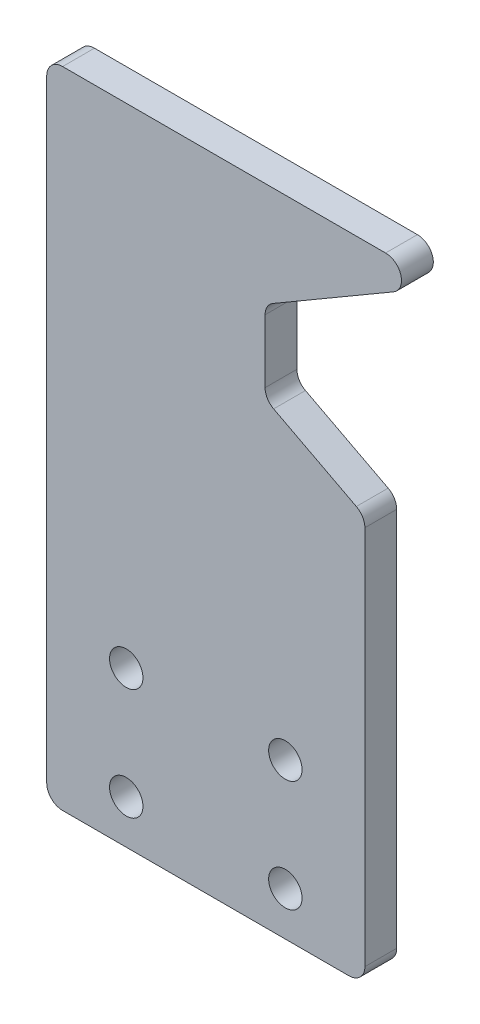
SolidWorks part; units mm, degrees
material "Thornel Mat VMA"
ref_plane "前视基准面" through (0, 0, 0) normal (0, 0, 1) x (1, 0, 0)
ref_plane "上视基准面" through (0, 0, 0) normal (0, 1, 0) x (1, 0, 0)
ref_plane "右视基准面" through (0, 0, 0) normal (1, 0, 0) x (0, 0, -1)
other "Configuration Table"
sketch "草图1" plane through (0, 0, 0) normal (0, 0, 1) x (1, 0, 0)
  line L0 (-20, 55.5) -> (-20, 25.5)
  line L2 (-20, 25.5) -> (-20, -25.5)
  line L3 (-20, -25.5) -> (20, -25.5)
  line L4 (20, 25.5) -> (20, -25.5)
  line L5 (-20, 25.5) -> (20, -25.5) construction
  line L6 (-20, -25.5) -> (20, 25.5) construction
  line L7 (-20, 25.5) -> (-5.963, 25.5)
  line L8 (-20, 55.5) -> (22.6016, 55.5)
  line L10 (23.6093, 51.7724) -> (7.4529, 42.3486)
  line L11 (7.4529, 42.3486) -> (7.4529, 32.0504)
  line L12 (7.4529, 32.0504) -> (20, 25.5)
  arc A0 (22.6016, 55.5) -> (23.6093, 51.7724) centre (22.6016, 53.5) cw
  point P0 (0, 0)
  point P19 (30, 55.5)
  dimension "D7" = 2
  dimension "D1" = 40
  dimension "D2" = 51
  dimension "D3" = 90
  dimension "D4" = 30
  dimension "D5" = 50
extrude "凸台-拉伸1" add sketch "草图1" along normal blind 4 contours L4 L2 L3 region at (-0.8936, 13.6527, 0)
sketch "草图2" plane through (0, 0, 4) normal (0, 0, 1) x (1, 0, 0)
  line L1 (-20, -25.5) -> (20, -25.5) construction
  line L2 (0, -25.5) -> (0, -4.5877) construction
  circle A0 centre (-10, -20) radius 2.1
  circle A1 centre (-10, -6) radius 2.1
  circle A2 centre (10, -6) radius 2.1
  circle A3 centre (10, -20) radius 2.1
  dimension "D2" = 5.5
  dimension "D1" = 4.2
  dimension "D3" = 20
  dimension "D5" = 14
extrude "切除-拉伸1" cut sketch "草图2" against normal up to next contours A1 | A0 | A2 | A3 region at (-10, -20, 4) region at (-10, -6, 4) region at (10, -6, 4) region at (10, -20, 4)
sketch "草图3" plane through (0, 0, 4) normal (0, 0, 1) x (1, 0, 0)
  line L1 (20, 25.5) -> (20, -25.5) construction
  circle A2 centre (-0.5, 14.8805) radius 10.5 construction
  circle A3 centre (10, 14.8805) radius 2.25
  circle A10 centre (-5.75, 5.7872) radius 2.25
  circle A11 centre (-5.75, 23.9738) radius 2.25
  point P13 (-0.5, 14.8805)
  dimension "D1" = 21
  dimension "D2" = 4.5
  dimension "D3" = 3
  dimension "D4" = 10
fillet "圆角1" radius 2 6 edges at (-20, 55.5, 2) (20, 25.5, 2) (20, -25.5, 2) (-20, -25.5, 2) (7.4529, 42.3486, 2) (7.4529, 32.0504, 2)
